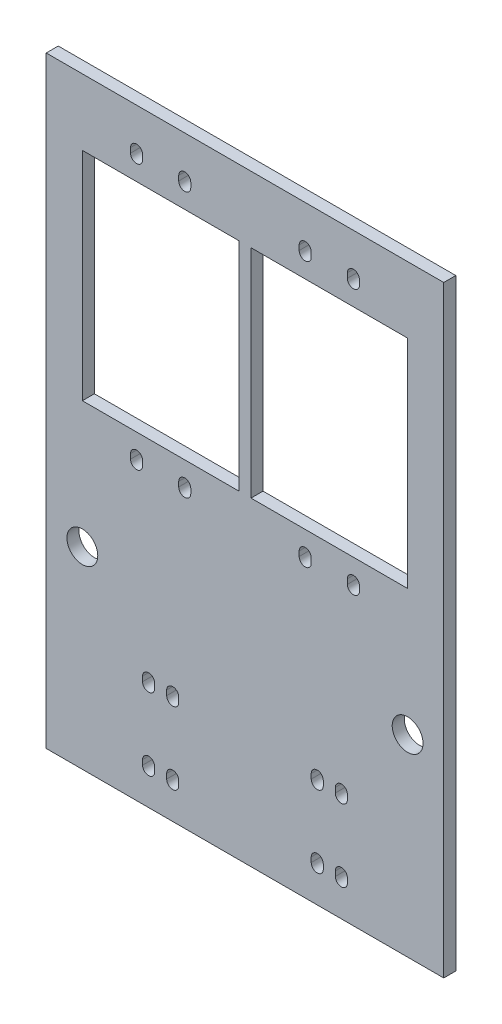
SolidWorks part; units mm, degrees
ref_plane "Front Plane" through (0, 0, 0) normal (0, 0, 1) x (1, 0, 0)
ref_plane "Top Plane" through (0, 0, 0) normal (0, 1, 0) x (1, 0, 0)
ref_plane "Right Plane" through (0, 0, 0) normal (1, 0, 0) x (0, 0, -1)
sketch "Sketch1" plane through (0, 0, 0) normal (0, 0, 1) x (1, 0, 0)
  line L1 (-104.775, 158.75) -> (104.775, 158.75)
  line L2 (-104.775, 158.75) -> (-104.775, -158.75)
  line L3 (-104.775, -158.75) -> (104.775, -158.75)
  line L4 (104.775, 158.75) -> (104.775, -158.75)
  line L5 (-104.775, 158.75) -> (104.775, -158.75) construction
  line L6 (-104.775, -158.75) -> (104.775, 158.75) construction
  point P0 (0, 0)
  dimension "D1" = 209.55
  dimension "D2" = 317.5
extrude "Boss-Extrude1" add sketch "Sketch1" along normal blind 6.35
sketch "Sketch2" plane through (0, 0, 6.35) normal (0, 0, 1) x (1, 0, 0)
  line L0 (0, 158.75) -> (0, -158.75) construction
  line L1 (-104.775, -158.75) -> (104.775, -158.75) construction
  line L2 (-85.725, 158.75) -> (-85.725, -158.75) construction
  line L3 (104.775, 158.75) -> (-104.775, 158.75) construction
  line L4 (-104.775, 158.75) -> (-104.775, -158.75) construction
  line L5 (-44.45, -139.7) -> (44.45, -139.7) construction
  line L6 (-50.8, -102.87) -> (-50.8, -100.33) construction
  line L7 (-38.1, -139.7) -> (-50.8, -139.7) construction
  line L8 (38.1, -139.7) -> (50.8, -139.7)
  line L9 (-44.45, -139.7) -> (-44.45, -101.6) construction
  line L10 (44.45, -139.7) -> (44.45, -101.6) construction
  line L11 (-50.8, -101.6) -> (-38.1, -101.6) construction
  line L12 (-53.975, -102.87) -> (-53.975, -100.33)
  line L13 (-47.625, -102.87) -> (-47.625, -100.33)
  line L14 (-38.1, -102.87) -> (-38.1, -100.33) construction
  line L15 (-34.925, -102.87) -> (-34.925, -100.33)
  line L16 (-41.275, -102.87) -> (-41.275, -100.33)
  line L17 (-44.45, -120.65) -> (-39.3755, -120.65) construction
  line L18 (-38.1, -138.43) -> (-38.1, -140.97) construction
  line L19 (-34.925, -138.43) -> (-34.925, -140.97)
  line L20 (-41.275, -138.43) -> (-41.275, -140.97)
  line L21 (-50.8, -138.43) -> (-50.8, -140.97) construction
  line L22 (-53.975, -138.43) -> (-53.975, -140.97)
  line L23 (-47.625, -138.43) -> (-47.625, -140.97)
  line L24 (50.8, -138.43) -> (50.8, -140.97) construction
  line L25 (53.975, -138.43) -> (53.975, -140.97)
  line L26 (47.625, -138.43) -> (47.625, -140.97)
  line L27 (38.1, -138.43) -> (38.1, -140.97) construction
  line L28 (34.925, -138.43) -> (34.925, -140.97)
  line L29 (41.275, -138.43) -> (41.275, -140.97)
  line L30 (38.1, -102.87) -> (38.1, -100.33) construction
  line L31 (34.925, -102.87) -> (34.925, -100.33)
  line L32 (41.275, -102.87) -> (41.275, -100.33)
  line L33 (50.8, -102.87) -> (50.8, -100.33) construction
  line L34 (53.975, -102.87) -> (53.975, -100.33)
  line L35 (47.625, -102.87) -> (47.625, -100.33)
  line L36 (-44.45, -101.6) -> (-44.45, 158.75) construction
  line L37 (44.45, -101.6) -> (44.45, 158.75) construction
  line L38 (-44.45, -120.65) -> (-44.45, 9.525) construction
  line L39 (-85.725, 9.525) -> (-3.175, 9.525)
  line L40 (-85.725, 9.525) -> (-85.725, 123.825)
  line L41 (-85.725, 123.825) -> (-3.175, 123.825)
  line L42 (-3.175, 123.825) -> (-3.175, 9.525)
  line L43 (-44.45, 136.525) -> (-31.75, 136.525) construction
  line L44 (-85.725, 66.675) -> (-44.45, 66.675) construction
  line L45 (-31.75, 137.795) -> (-31.75, 135.255) construction
  line L46 (-28.575, 137.795) -> (-28.575, 135.255)
  line L47 (-34.925, 137.795) -> (-34.925, 135.255)
  line L48 (-57.15, 137.795) -> (-57.15, 135.255) construction
  line L49 (-60.325, 137.795) -> (-60.325, 135.255)
  line L50 (-53.975, 137.795) -> (-53.975, 135.255)
  line L51 (-31.75, -4.445) -> (-31.75, -1.905) construction
  line L52 (-28.575, -4.445) -> (-28.575, -1.905)
  line L53 (-34.925, -4.445) -> (-34.925, -1.905)
  line L54 (-57.15, -4.445) -> (-57.15, -1.905) construction
  line L55 (-60.325, -4.445) -> (-60.325, -1.905)
  line L56 (-53.975, -4.445) -> (-53.975, -1.905)
  line L57 (31.75, -4.445) -> (31.75, -1.905) construction
  line L58 (28.575, -4.445) -> (28.575, -1.905)
  line L59 (34.925, -4.445) -> (34.925, -1.905)
  line L60 (57.15, -4.445) -> (57.15, -1.905) construction
  line L61 (60.325, -4.445) -> (60.325, -1.905)
  line L62 (53.975, -4.445) -> (53.975, -1.905)
  line L63 (85.725, 9.525) -> (3.175, 9.525)
  line L64 (3.175, 123.825) -> (3.175, 9.525)
  line L65 (85.725, 123.825) -> (3.175, 123.825)
  line L66 (85.725, 9.525) -> (85.725, 123.825)
  line L67 (31.75, 137.795) -> (31.75, 135.255) construction
  line L68 (28.575, 137.795) -> (28.575, 135.255)
  line L69 (34.925, 137.795) -> (34.925, 135.255)
  line L70 (57.15, 137.795) -> (57.15, 135.255) construction
  line L71 (60.325, 137.795) -> (60.325, 135.255)
  line L72 (53.975, 137.795) -> (53.975, 135.255)
  circle A1 centre (-85.725, -57.15) radius 8.128
  circle A4 centre (85.725, -57.15) radius 8.128
  arc A6 (-53.975, -102.87) -> (-47.625, -102.87) centre (-50.8, -102.87) ccw
  arc A7 (-47.625, -100.33) -> (-53.975, -100.33) centre (-50.8, -100.33) ccw
  arc A8 (-34.925, -102.87) -> (-41.275, -102.87) centre (-38.1, -102.87) cw
  arc A9 (-41.275, -100.33) -> (-34.925, -100.33) centre (-38.1, -100.33) cw
  arc A10 (-34.925, -138.43) -> (-41.275, -138.43) centre (-38.1, -138.43) ccw
  arc A11 (-41.275, -140.97) -> (-34.925, -140.97) centre (-38.1, -140.97) ccw
  arc A12 (-53.975, -138.43) -> (-47.625, -138.43) centre (-50.8, -138.43) cw
  arc A13 (-47.625, -140.97) -> (-53.975, -140.97) centre (-50.8, -140.97) cw
  arc A14 (53.975, -138.43) -> (47.625, -138.43) centre (50.8, -138.43) ccw
  arc A15 (47.625, -140.97) -> (53.975, -140.97) centre (50.8, -140.97) ccw
  arc A16 (34.925, -138.43) -> (41.275, -138.43) centre (38.1, -138.43) cw
  arc A17 (41.275, -140.97) -> (34.925, -140.97) centre (38.1, -140.97) cw
  arc A18 (34.925, -102.87) -> (41.275, -102.87) centre (38.1, -102.87) ccw
  arc A19 (41.275, -100.33) -> (34.925, -100.33) centre (38.1, -100.33) ccw
  arc A20 (53.975, -102.87) -> (47.625, -102.87) centre (50.8, -102.87) cw
  arc A21 (47.625, -100.33) -> (53.975, -100.33) centre (50.8, -100.33) cw
  arc A23 (-28.575, 137.795) -> (-34.925, 137.795) centre (-31.75, 137.795) ccw
  arc A24 (-34.925, 135.255) -> (-28.575, 135.255) centre (-31.75, 135.255) ccw
  arc A25 (-60.325, 137.795) -> (-53.975, 137.795) centre (-57.15, 137.795) cw
  arc A26 (-53.975, 135.255) -> (-60.325, 135.255) centre (-57.15, 135.255) cw
  arc A27 (-28.575, -4.445) -> (-34.925, -4.445) centre (-31.75, -4.445) cw
  arc A28 (-34.925, -1.905) -> (-28.575, -1.905) centre (-31.75, -1.905) cw
  arc A29 (-60.325, -4.445) -> (-53.975, -4.445) centre (-57.15, -4.445) ccw
  arc A30 (-53.975, -1.905) -> (-60.325, -1.905) centre (-57.15, -1.905) ccw
  arc A31 (28.575, -4.445) -> (34.925, -4.445) centre (31.75, -4.445) ccw
  arc A32 (34.925, -1.905) -> (28.575, -1.905) centre (31.75, -1.905) ccw
  arc A33 (60.325, -4.445) -> (53.975, -4.445) centre (57.15, -4.445) cw
  arc A34 (53.975, -1.905) -> (60.325, -1.905) centre (57.15, -1.905) cw
  arc A35 (28.575, 137.795) -> (34.925, 137.795) centre (31.75, 137.795) cw
  arc A36 (34.925, 135.255) -> (28.575, 135.255) centre (31.75, 135.255) cw
  arc A37 (60.325, 137.795) -> (53.975, 137.795) centre (57.15, 137.795) ccw
  arc A38 (53.975, 135.255) -> (60.325, 135.255) centre (57.15, 135.255) ccw
  point P6 (0, 0)
  point P19 (-31.75, 136.525)
  point P28 (0, -139.7)
  point P31 (-44.45, -139.7)
  point P34 (44.45, -139.7)
  point P39 (-44.45, -101.6)
  point P40 (-50.8, -101.6)
  point P47 (-38.1, -101.6)
  point P56 (-38.1, -139.7)
  point P63 (-50.8, -139.7)
  point P70 (50.8, -139.7)
  point P77 (38.1, -139.7)
  point P84 (38.1, -101.6)
  point P91 (50.8, -101.6)
  point P102 (-44.45, 9.525)
  point P109 (-57.15, 136.525)
  point P116 (-31.75, -3.175)
  point P123 (-57.15, -3.175)
  point P130 (31.75, -3.175)
  point P137 (57.15, -3.175)
  point P148 (31.75, 136.525)
  point P155 (57.15, 136.525)
  dimension "D2" = 12.7
  dimension "D3" = 16.256
  dimension "D4" = 12.7
  dimension "D12" = 3.175
  dimension "D5" = 2.54
  dimension "D6" = 3.175
  dimension "D17" = 101.6
  dimension "D1" = 19.05
  dimension "D7" = 19.05
  dimension "D8" = 88.9
  dimension "D9" = 12.7
  dimension "D10" = 12.7
  dimension "D11" = 38.1
  dimension "D13" = 2.54
  dimension "D14" = 130.175
  dimension "D15" = 82.55
  dimension "D16" = 114.3
extrude "Cut-Extrude2" cut sketch "Sketch2" against normal blind 6.35 contours L42 L41 L40 L39 | L63 L66 L65 L64 | A26 L50 A25 L49 | L47 A24 L46 A23 | A36 L69 A35 L68 | L72 A38 L71 A37 | L56 A30 L55 A29 | A28 L53 A27 L52 | L59 A32 L58 A31 | A34 L62 A33 L61 | L13 A7 L12 A6 | A9 L16 A8 L15 | A13 L23 A12 L22 | L20 A11 L19 A10 | A17 L29 A16 L28 | L26 A15 L25 A14 | A21 L35 A20 L34 | L32 A19 L31 A18 | A1 | A4 region at (47.7342, -139.065, 6.35) region at (41.1658, -140.335, 6.35) region at (-50.8, -101.6, 6.35) region at (-38.1, -101.6, 6.35) region at (-38.1, -139.7, 6.35) region at (-50.8, -139.7, 6.35) region at (38.1, -101.6, 6.35) region at (50.8, -101.6, 6.35) region at (-44.45, 66.675, 6.35) region at (-31.75, 136.525, 6.35) region at (-57.15, 136.525, 6.35) region at (-31.75, -3.175, 6.35) region at (-57.15, -3.175, 6.35) region at (31.75, -3.175, 6.35) region at (57.15, -3.175, 6.35) region at (44.45, 66.675, 6.35) region at (31.75, 136.525, 6.35) region at (57.15, 136.525, 6.35) region at (-85.725, -57.15, 6.35) region at (85.725, -57.15, 6.35)
